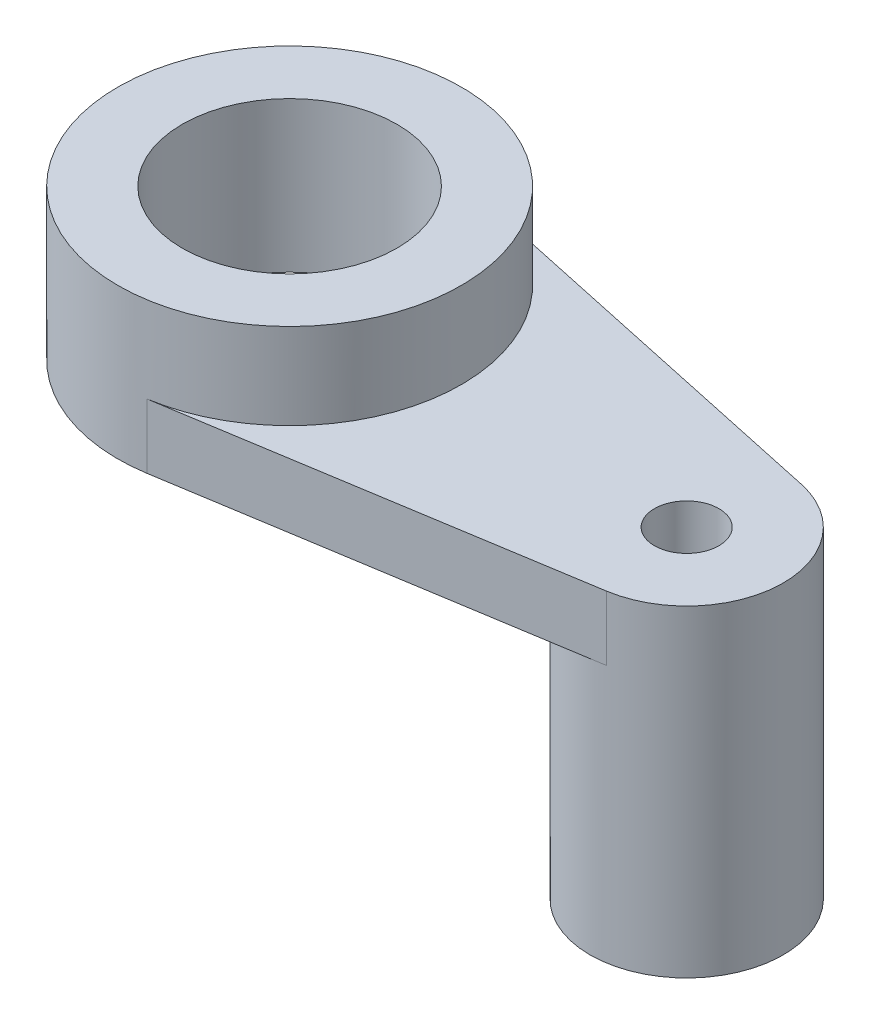
SolidWorks part; units mm, degrees
ref_plane "Front Plane" through (0, 0, 0) normal (0, 0, 1) x (1, 0, 0)
ref_plane "Top Plane" through (0, 0, 0) normal (0, 1, 0) x (1, 0, 0)
ref_plane "Right Plane" through (0, 0, 0) normal (1, 0, 0) x (0, 0, -1)
sketch "Sketch1" plane through (0, 0, 0) normal (0, 1, 0) x (1, 0, 0)
  line L0 (39.8789, 7.7892) -> (3.3642, 15.6423)
  line L1 (39.4089, -9.8965) -> (2.5285, -15.7989)
  circle A0 centre (0, 0) radius 10
  circle A1 centre (0, 0) radius 16
  circle A2 centre (37.9866, -1.0096) radius 3
  circle A3 centre (37.9866, -1.0096) radius 9
  dimension "D1" = 38
  dimension "D2" = 20
  dimension "D3" = 6
  dimension "D4" = 6
  dimension "D5" = 18
extrude "Boss-Extrude1" add sketch "Sketch1" along normal blind 6 contours A3 L0 A1 L1 | A3 A2 region at (21.9173, 0, 0.5825) region at (44.7897, 0, -4.4859)
extrude "Boss-Extrude2" add sketch "Sketch1<3>" against normal blind 24 contours A3 A2 region at (44.7897, 0, -4.4859)
sketch "Sketch1<3>" plane through (0, 0, 0) normal (0, 1, 0) x (1, 0, 0) same geometry as "Sketch1"
extrude "Boss-Extrude3" add sketch "Sketch1<4>" along normal blind 14 contours A1 A0 region at (12.0944, 0, -9.7698)
sketch "Sketch1<4>" plane through (0, 0, 0) normal (0, 1, 0) x (1, 0, 0) same geometry as "Sketch1"
